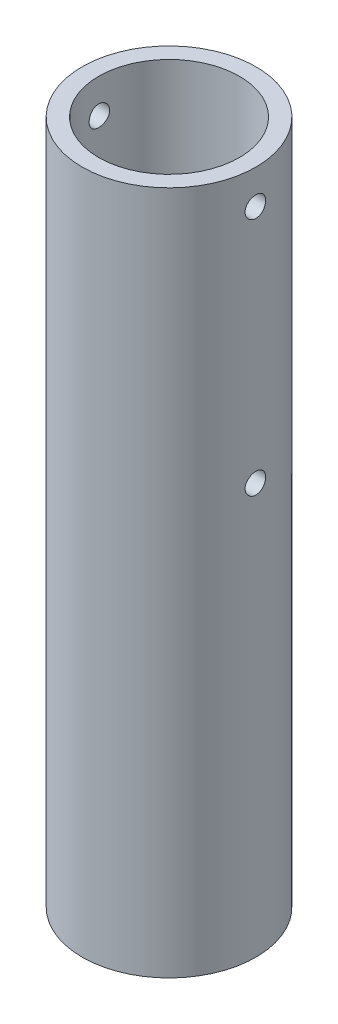
SolidWorks part; units mm, degrees
material "AISI 4130 Steel, annealed at 865C"
ref_plane "Front Plane" through (0, 0, 0) normal (0, 0, 1) x (1, 0, 0)
ref_plane "Top Plane" through (0, 0, 0) normal (0, 1, 0) x (1, 0, 0)
ref_plane "Right Plane" through (0, 0, 0) normal (1, 0, 0) x (0, 0, -1)
sketch "Sketch1" plane through (0, 0, 0) normal (0, 1, 0) x (1, 0, 0)
  circle A0 centre (0, 0) radius 12.7
  circle A1 centre (0, 0) radius 10.287
  dimension "D1" = 25.4
  dimension "D2" = 2.413
extrude "Boss-Extrude1" add sketch "Sketch1" along normal blind 100
sketch "Sketch2" plane through (0, 0, 0) normal (1, 0, 0) x (0, 0, -1)
  line L0 (0, 100) -> (0, 0) construction
  line L1 (12.7, 100) -> (-12.7, 100) construction
  circle A0 centre (0, 95) radius 1.5
  circle A1 centre (0, 60) radius 1.5
  dimension "D3" = 3
  dimension "D1" = 5
  dimension "D2" = 35
extrude "Cut-Extrude1" cut sketch "Sketch2" against normal blind 20 and the other way blind 20
